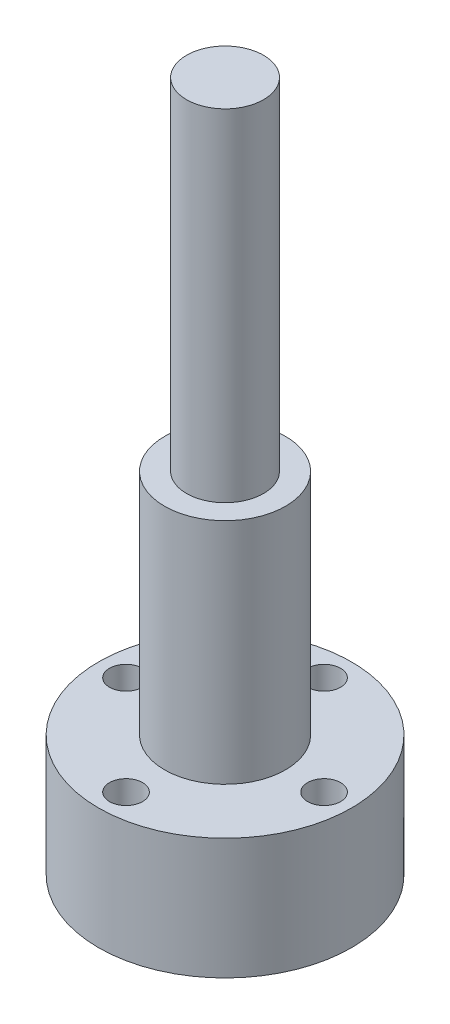
SolidWorks part; units mm, degrees
material "1023 Arkusz stali węglowej (SS)"
ref_plane "Płaszczyzna przednia" through (0, 0, 0) normal (0, 0, 1) x (1, 0, 0)
ref_plane "Płaszczyzna górna" through (0, 0, 0) normal (0, 1, 0) x (1, 0, 0)
ref_plane "Płaszczyzna prawa" through (0, 0, 0) normal (1, 0, 0) x (0, 0, -1)
sketch "Szkic1" plane through (0, 0, 0) normal (0, 0, 1) x (1, 0, 0)
  line L0 (-7, 2) -> (-7, 0)
  line L1 (-23, 2) -> (-7, 2)
  line L2 (-23, 24) -> (-23, 2)
  line L3 (-23, 24) -> (-11, 24)
  line L4 (-11, 65.5) -> (-11, 24)
  line L5 (-7, 65.5) -> (-7, 127.5)
  line L6 (-11, 65.5) -> (-7, 65.5)
  line L7 (0, 127.5) -> (0, 0)
  line L8 (-7, 0) -> (0, 0)
  line L9 (0, 127.5) -> (-7, 127.5)
revolve "Obrót1" add sketch "Szkic1" angle 360 about L7
sketch "Szkic2" plane through (0, 2, 0) normal (0, -1, 0) x (1, 0, 0)
  circle A0 centre (0, 18) radius 3
  circle A1 centre (18, 0) radius 3
  circle A2 centre (0, -18) radius 3
  circle A3 centre (-18, 0) radius 3
  point P12 (0, 2)
  point P13 (0, 0)
  dimension "D1" = 6
  dimension "D2" = 18
  dimension "D3" = 4
extrude "Wytnij-wyciągnięcie1" cut sketch "Szkic2" against normal through all
